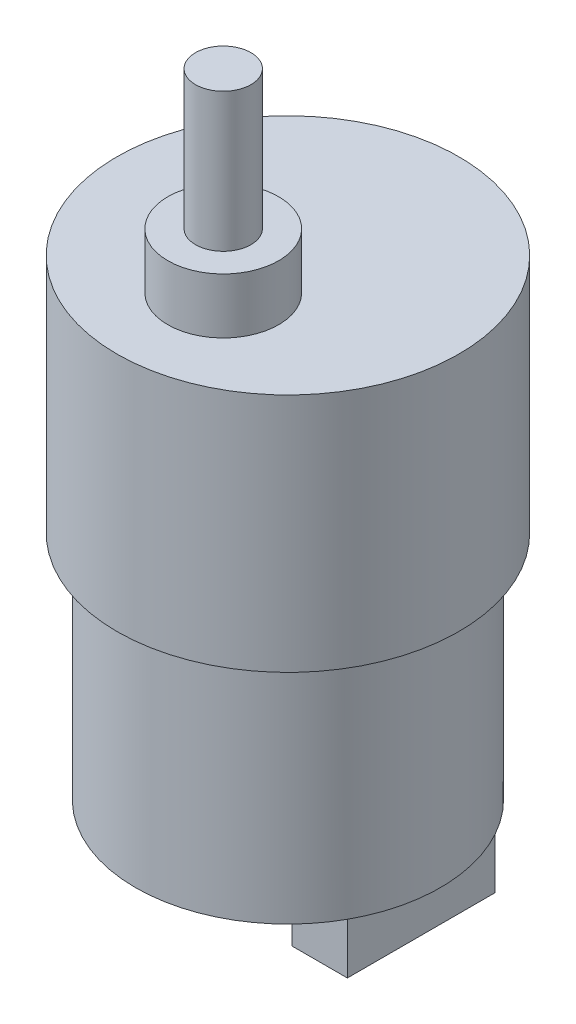
SolidWorks part; units mm, degrees
ref_plane "Front Plane" through (0, 0, 0) normal (0, 0, 1) x (1, 0, 0)
ref_plane "Top Plane" through (0, 0, 0) normal (0, 1, 0) x (1, 0, 0)
ref_plane "Right Plane" through (0, 0, 0) normal (1, 0, 0) x (0, 0, -1)
ref_plane "Plane1" through (0, 0, 7) normal (0, 0, 1) x (1, 0, 0)
sketch "Sketch1" plane through (0, 0, 0) normal (0, 1, 0) x (1, 0, 0)
  line L0 (-20.35, -7) -> (20.35, -7) construction
  line L2 (8.4309, -8) -> (14.4309, -8)
  line L3 (8.4309, -8) -> (8.4309, 8)
  line L4 (8.4309, 8) -> (14.4309, 8)
  line L5 (14.4309, -8) -> (14.4309, 8)
  line L6 (8.4309, -8) -> (14.4309, 8) construction
  line L7 (8.4309, 8) -> (14.4309, -8) construction
  circle A0 centre (0, 0) radius 18.5
  circle A1 centre (0, 0) radius 16.5
  circle A2 centre (0, -7) radius 6
  circle A3 centre (0, -7) radius 3
  circle A4 centre (0, 0) radius 4.5
  point P9 (11.4309, 0)
  dimension "D1" = 37
  dimension "D2" = 33
  dimension "D3" = 12
  dimension "D4" = 6
  dimension "D5" = 9
  dimension "D6" = 16
  dimension "D7" = 6
extrude "Boss-Extrude1" add sketch "Sketch1" against normal blind 26 contours A0 A1 | L4 A1 L2 L3 A4 A2 | A2 A4 | L2 L5 L4 L3 | L5 A1 | A4 A3 A2 | A4 A3 | A3 A4 A2 | A3 A4 region at (11.4309, 0, 0) region at (11.4309, 0, 8.4523) region at (15.2631, 0, 0) region at (-17.9767, 0, 0) region at (-2.4878, 0, 12.2833) region at (0, 0, 2.6181) region at (0, 0, -1.1188) region at (0, 0, 4.2602) region at (0, 0, 7.0884)
extrude "Boss-Extrude2" add sketch "Sketch1<3>" against normal blind 25 from surface contours L4 A1 L2 L3 A4 A2 | A2 A4 | L2 L5 L4 L3 | A3 A4 A2 | A3 A4 | A4 A3 | A4 A3 A2 | A1 region at (11.4309, 0, 0) region at (11.4309, 0, 8.4523) region at (-2.4878, 0, 12.2833) region at (0, 0, 2.6181) region at (0, 0, -1.1188) region at (0, 0, 4.2602) region at (0, 0, 7.0884) starting at face at (0, -26, 18.5)
sketch "Sketch1<3>" plane through (0, 0, 0) normal (0, 1, 0) x (1, 0, 0) same geometry as "Sketch1"
extrude "Boss-Extrude3" add sketch "Sketch1<4>" against normal blind 5.5 from surface contours L2 L5 L4 L3 region at (11.4309, 0, 0) starting at face at (0, -51, 16.5)
sketch "Sketch1<4>" plane through (0, 0, 0) normal (0, 1, 0) x (1, 0, 0) same geometry as "Sketch1"
extrude "Boss-Extrude4" add sketch "Sketch1<5>" against normal blind 8.5 from surface contours A2 A4 | A3 A4 A2 | A3 A4 region at (0, 0, 2.6181) region at (0, 0, -1.1188) region at (0, 0, 4.2602) starting at face at (3.6982, -51, 0)
sketch "Sketch1<5>" plane through (0, 0, 0) normal (0, 1, 0) x (1, 0, 0) same geometry as "Sketch1"
extrude "Boss-Extrude5" add sketch "Sketch1<6>" along normal blind 6 contours A4 A3 A2 | A4 A3 | A3 A4 A2 | A3 A4 region at (-2.4878, 0, 12.2833) region at (0, 0, 2.6181) region at (0, 0, 4.2602) region at (0, 0, 7.0884)
sketch "Sketch1<6>" plane through (0, 0, 0) normal (0, 1, 0) x (1, 0, 0) same geometry as "Sketch1"
extrude "Boss-Extrude6" add sketch "Sketch1<7>" along normal blind 15 from surface contours A4 A3 | A3 A4 region at (0, 0, 4.2602) region at (0, 0, 7.0884) starting at face at (0, 6, 13)
sketch "Sketch1<7>" plane through (0, 0, 0) normal (0, 1, 0) x (1, 0, 0) same geometry as "Sketch1"
